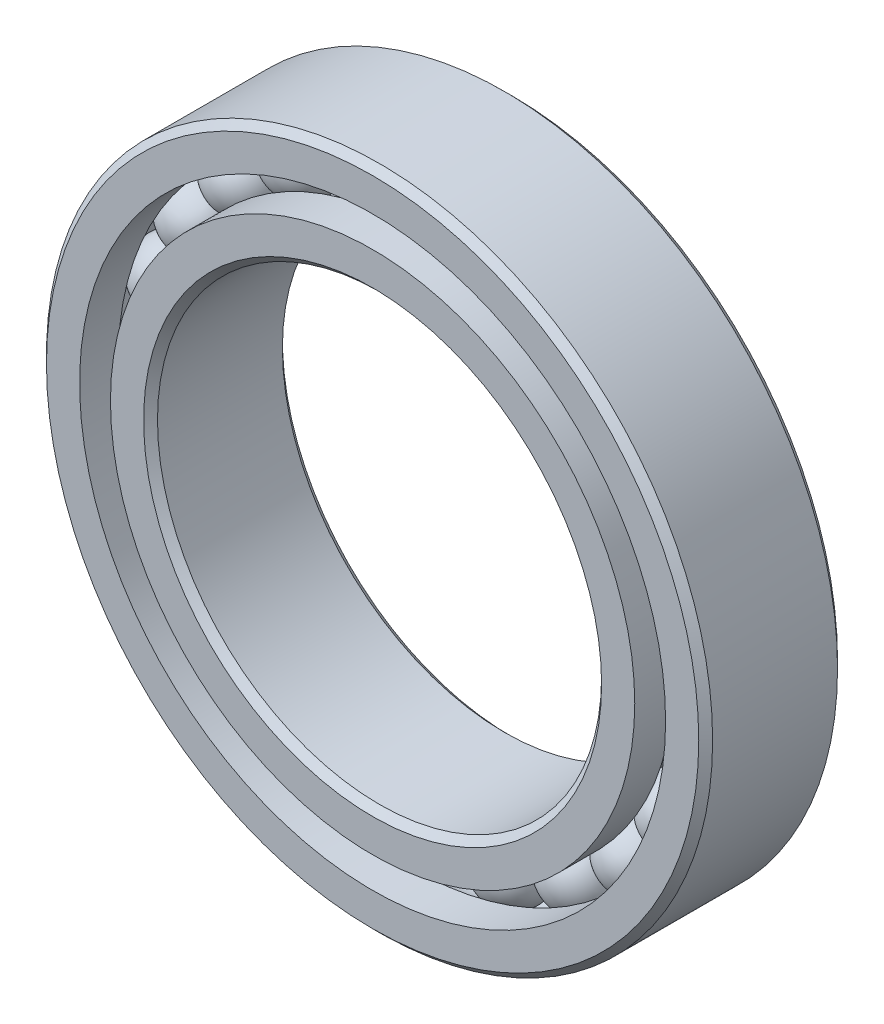
SolidWorks part; units mm, degrees
ref_plane "Front Plane" through (0, 0, 0) normal (0, 0, 1) x (1, 0, 0)
ref_plane "Top Plane" through (0, 0, 0) normal (0, 1, 0) x (1, 0, 0)
ref_plane "Right Plane" through (0, 0, 0) normal (1, 0, 0) x (0, 0, -1)
sketch "Sketch1" plane through (0, 0, 0) normal (1, 0, 0) x (0, 0, -1)
  line L0 (-1.25, 0) -> (1.25, 0) construction
  line L1 (0, 6) -> (0, -6) construction
  line L2 (1.125, 6) -> (-1.125, 6) construction
  line L3 (-1.125, 6) -> (-1.25, 5.875) construction
  line L4 (-1.25, 5.875) -> (-1.25, 5.2778) construction
  line L5 (-1.25, 5.2778) -> (-0.5556, 5.2778) construction
  line L6 (1.25, 5.2778) -> (0.5556, 5.2778) construction
  line L7 (1.25, 5.875) -> (1.25, 5.2778) construction
  line L8 (1.125, 6) -> (1.25, 5.875) construction
  line L9 (0, 6) -> (0, 5) construction
  line L10 (0, 5) -> (0, 4) construction
  arc A0 (-0.5556, 5.2778) -> (0.5556, 5.2778) centre (0, 5) cw construction
  arc A1 (-0.5556, 5.2778) -> (0.5556, 5.2778) centre (0, 5) ccw construction
  point P14 (0, 4)
  point P15 (0, -4)
  dimension "Width" = 2.5
  dimension "OD" = 12
  dimension "D1" = 45
  dimension "D2" = 0.125
  dimension "D3" = 1.1111
  dimension "Shaft Dia" = 8
  dimension "D4" = 0.2778
sketch "Sketch2" plane through (0, 0, 0) normal (1, 0, 0) x (0, 0, -1)
  line L0 (-1.25, 4.7222) -> (-0.5556, 4.7222)
  line L2 (-1.25, 4.7222) -> (-1.25, 4.125)
  line L3 (-1.25, 4.125) -> (-1.125, 4)
  line L4 (-1.125, 4) -> (1.125, 4)
  line L5 (0, 6) -> (0, -6) construction
  line L6 (0, 4) -> (0, 4.3789) construction
  line L7 (0, 4.3789) -> (0, 4) construction
  line L9 (-1.25, 5.875) -> (-1.25, 5.2778) construction
  line L10 (1.25, 4.7222) -> (0.5556, 4.7222)
  line L11 (1.25, 4.7222) -> (1.25, 4.125)
  line L12 (1.25, 4.125) -> (1.125, 4)
  line L13 (1.125, 6) -> (1.25, 5.875) construction
  line L14 (1.25, 5.875) -> (1.25, 5.2778) construction
  line L15 (1.25, 5.2778) -> (0.5556, 5.2778) construction
  line L16 (-1.25, 5.2778) -> (-0.5556, 5.2778) construction
  line L17 (1.125, 6) -> (-1.125, 6) construction
  line L18 (-1.125, 6) -> (-1.25, 5.875) construction
  line L19 (1.125, 6) -> (1.25, 5.875)
  line L20 (1.25, 5.875) -> (1.25, 5.2778)
  line L21 (1.25, 5.2778) -> (0.5556, 5.2778)
  line L22 (-1.25, 5.2778) -> (-0.5556, 5.2778)
  line L23 (-1.25, 5.875) -> (-1.25, 5.2778)
  line L24 (1.125, 6) -> (-1.125, 6)
  line L25 (-1.125, 6) -> (-1.25, 5.875)
  line L26 (-1.25, 4.125) -> (-1.125, 4.125) construction
  line L27 (-1.125, 4.125) -> (-1.125, 4) construction
  arc A0 (-0.5556, 4.7222) -> (0.5556, 4.7222) centre (0, 5) ccw
  arc A1 (0.5556, 5.2778) -> (-0.5556, 5.2778) centre (0, 5) ccw construction
  circle A2 centre (0, 5) radius 0.6211 construction
  arc A3 (-0.5556, 5.2778) -> (0.5556, 5.2778) centre (0, 5) cw
  dimension "D1" = 0.125
revolve "Revolve1" add sketch "Sketch2" angle 360 about L0
sketch "Sketch3" plane through (0, 0, 0) normal (1, 0, 0) x (0, 0, -1)
  line L0 (-0.6211, 5) -> (0.6211, 5)
  line L1 (0, 5) -> (0, 0) construction
  circle A1 centre (0, 5) radius 0.6211 construction
  arc A2 (-0.6211, 5) -> (0.6211, 5) centre (0, 5) cw
  arc A3 (0.5556, 5.2778) -> (-0.5556, 5.2778) centre (0, 5) ccw construction
  dimension "D1" = 1.2423
  dimension "D2" = 5
revolve "Revolve2" add sketch "Sketch3" angle 360 about L0
ref_axis "Axis1" through (0, 0, -1.25) along (0, 0, 1)
pattern_circular "CirPattern1" count 24 every 15 about axis through (0, 0, -1.25) along (0, 0, 1) of bodies 104
sketch "Sketch6" plane through (0, 0, 0) normal (0, 1, 0) x (1, 0, 0)
  point P0 (6, -1.25)
  point P1 (6, 1.25)
  dimension "D1" = 2.5
equation "\"D2@Sketch1\" = \"Width@Sketch1\"*.05"
equation "\"D3@Sketch1\" = \"Width@Sketch1\"/2.25"
equation "\"D4@Sketch1\" = \"D3@Sketch1\"/4"
equation "\"Balls@CirPattern1\"=\"D2@Sketch3\"*2*pi/\"D1@Sketch3\"-1"
equation "\"D2@CirPattern1\" = 360/\"Balls@CirPattern1\""
equation "\"D1@Sketch2\"=\"D2@Sketch1\""
equation "\"D1@Sketch6\"=\"Width@Sketch1\""
